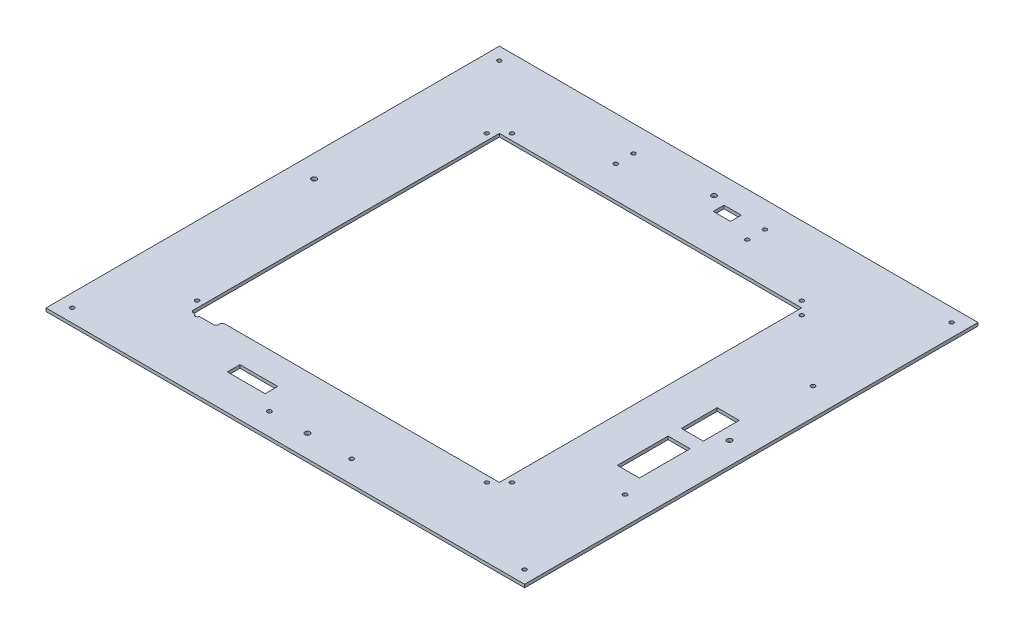
SolidWorks part; units mm, degrees
ref_plane "Front" through (0, 0, 0) normal (0, 0, 1) x (1, 0, 0)
ref_plane "Top" through (0, 0, 0) normal (0, 1, 0) x (1, 0, 0)
ref_plane "Right" through (0, 0, 0) normal (1, 0, 0) x (0, 0, -1)
sketch "Sketch1" plane through (0, 0, 0) normal (0, 1, 0) x (1, 0, 0)
  line L0 (-55, 0) -> (55, 0) construction
  line L1 (-242.5515, 228.6) -> (240.0485, 228.6)
  line L2 (-242.5515, 228.6) -> (-242.5515, -228.6)
  line L3 (-242.5515, -228.6) -> (240.0485, -228.6)
  line L4 (240.0485, 228.6) -> (240.0485, -228.6)
  line L5 (-242.5515, 228.6) -> (240.0485, -228.6) construction
  line L6 (-242.5515, -228.6) -> (240.0485, 228.6) construction
  line L7 (-166.3515, 152.4) -> (138.4485, 152.4)
  line L8 (-166.3515, 152.4) -> (-166.3515, -152.4)
  line L9 (-166.3515, -152.4) -> (138.4485, -152.4)
  line L10 (138.4485, 152.4) -> (138.4485, -152.4)
  line L11 (-166.3515, 152.4) -> (138.4485, -152.4) construction
  line L12 (-166.3515, -152.4) -> (138.4485, 152.4) construction
  line L13 (-160.0015, 146.05) -> (132.0985, 146.05)
  line L14 (-160.0015, 146.05) -> (-160.0015, -146.05)
  line L15 (-160.0015, -146.05) -> (132.0985, -146.05)
  line L16 (132.0985, 146.05) -> (132.0985, -146.05)
  line L17 (-160.0015, 146.05) -> (132.0985, -146.05) construction
  line L18 (-160.0015, -146.05) -> (132.0985, 146.05) construction
  line L19 (-166.3515, -152.4) -> (-140.9515, -152.4)
  line L20 (-166.3515, -152.4) -> (-166.3515, -158.75)
  line L21 (-166.3515, -158.75) -> (-140.9515, -158.75)
  line L22 (-140.9515, -152.4) -> (-140.9515, -158.75)
  line L23 (-242.5515, 0) -> (240.0485, 0) construction
  line L28 (182.9854, -26.8512) -> (205.1825, -26.8512)
  line L29 (182.9854, -26.8512) -> (182.9854, -78.0068)
  line L30 (182.9854, -78.0068) -> (205.1825, -78.0068)
  line L31 (205.1825, -26.8512) -> (205.1825, -78.0068)
  line L32 (182.9854, -13.5376) -> (205.1825, -13.5376)
  line L33 (182.9854, -13.5376) -> (182.9854, 22.6879)
  line L34 (182.9854, 22.6879) -> (205.1825, 22.6879)
  line L35 (205.1825, -13.5376) -> (205.1825, 22.6879)
  line L40 (27.0379, 202.954) -> (9.5991, 202.954)
  line L41 (27.0379, 202.954) -> (27.0379, 192.0704)
  line L42 (27.0379, 192.0704) -> (9.5991, 192.0704)
  line L43 (9.5991, 202.954) -> (9.5991, 192.0704)
  line L44 (-95.2315, -180.3456) -> (-57.1315, -180.3456)
  line L45 (-95.2315, -180.3456) -> (-95.2315, -193.0456)
  line L46 (-95.2315, -193.0456) -> (-57.1315, -193.0456)
  line L47 (-57.1315, -180.3456) -> (-57.1315, -193.0456)
  circle A0 centre (51.3519, 202.311) radius 2
  circle A1 centre (51.3519, 184.531) radius 2
  circle A2 centre (-81.1091, 202.311) radius 2
  circle A3 centre (-81.1091, 184.531) radius 2
  circle A4 centre (212.3904, -99.5798) radius 2.0955
  circle A5 centre (212.3904, 89.828) radius 2.0955
  circle A6 centre (-39.6436, -206.2861) radius 2.1
  circle A7 centre (43.3382, -206.2861) radius 2.1
  circle A8 centre (-172.7335, 146.082) radius 2
  circle A9 centre (-160.0335, 158.782) radius 2
  circle A12 centre (-160.0335, -158.782) radius 2
  circle A13 centre (-172.7335, -146.082) radius 2
  circle A14 centre (132.1305, 158.782) radius 2
  circle A15 centre (144.8305, 146.082) radius 2
  circle A16 centre (144.8305, -146.082) radius 2
  circle A17 centre (132.1305, -158.782) radius 2
  circle A18 centre (-229.8327, 215.8812) radius 2
  circle A19 centre (226.7201, 215.2716) radius 2
  circle A20 centre (-229.3755, -215.2716) radius 2
  circle A21 centre (227.2281, -215.9066) radius 2
  circle A22 centre (-220.0871, 19.264) radius 2.54
  circle A23 centre (-1.2915, -206.2372) radius 2.54
  circle A24 centre (-3.8315, 206.2626) radius 2.54
  circle A25 centre (217.7111, 0.294) radius 2.54
  point P0 (-1.2515, 0)
  point P6 (-44.5662, -1.1741)
  point P11 (-84.1987, 3.6789)
  point P21 (-13.9515, 0)
  point P22 (-13.9515, 0)
  point P23 (-1.2515, 0)
  dimension "D15" = 4
  dimension "D16" = 4
  dimension "D17" = 26.289
  dimension "D18" = 17.78
  dimension "D19" = 188.6966
  dimension "D20" = 132.461
  dimension "D22" = 27.6581
  dimension "D23" = 4.191
  dimension "D24" = 129.0202
  dimension "D26" = 4.2
  dimension "D27" = 22.3139
  dimension "D28" = 202.9079
  dimension "D29" = 82.9818
  dimension "D33" = 69.818
  dimension "D34" = 82.518
  dimension "D35" = 4
  dimension "D36" = 69.818
  dimension "D37" = 82.518
  dimension "D38" = 4
  dimension "D39" = 107.918
  dimension "D40" = 69.818
  dimension "D41" = 95.218
  dimension "D42" = 82.518
  dimension "D43" = 95.218
  dimension "D44" = 82.518
  dimension "D45" = 69.818
  dimension "D46" = 107.918
  dimension "D47" = 4
  dimension "D48" = 4
  dimension "D49" = 4
  dimension "D50" = 4
  dimension "D51" = 12.7188
  dimension "D53" = 13.3284
  dimension "D54" = 13.3284
  dimension "D55" = 13.176
  dimension "D56" = 13.3284
  dimension "D57" = 4
  dimension "D58" = 4
  dimension "D59" = 4
  dimension "D60" = 12.8204
  dimension "D61" = 4
  dimension "D62" = 12.6934
  dimension "D63" = 22.4644
  dimension "D64" = 247.864
  dimension "D65" = 22.3628
  dimension "D66" = 241.26
  dimension "D67" = 5.08
  dimension "D68" = 5.08
  dimension "D69" = 5.08
  dimension "D70" = 22.3374
  dimension "D71" = 238.72
  dimension "D72" = 22.3374
  dimension "D73" = 228.306
  dimension "D74" = 5.08
  dimension "D1" = 457.2
  dimension "D2" = 482.6
  dimension "D3" = 304.8
  dimension "D4" = 304.8
  dimension "D5" = 76.2
  dimension "D6" = 292.1
  dimension "D7" = 146.05
  dimension "D8" = 228.6
  dimension "D9" = 25.4
  dimension "D10" = 6.35
  dimension "D21" = 17.78
  dimension "D25" = 189.4078
  dimension "D30" = 12.7
  dimension "D31" = 185.42
  dimension "D32" = 38.1
  dimension "D52" = 12.7188
extrude "Boss-Extrude1" add sketch "Sketch1" along normal blind 3.175 contours L4 L1 L2 L3 L7 L10 L9 L8 region at (-1.2515, 0, -221.9522)
fillet "Fillet1" radius 2.54 3 edges at (-140.9515, 1.5875, 158.75) (-166.3515, 1.5875, 158.75) (-140.9515, 1.5875, 152.4)
